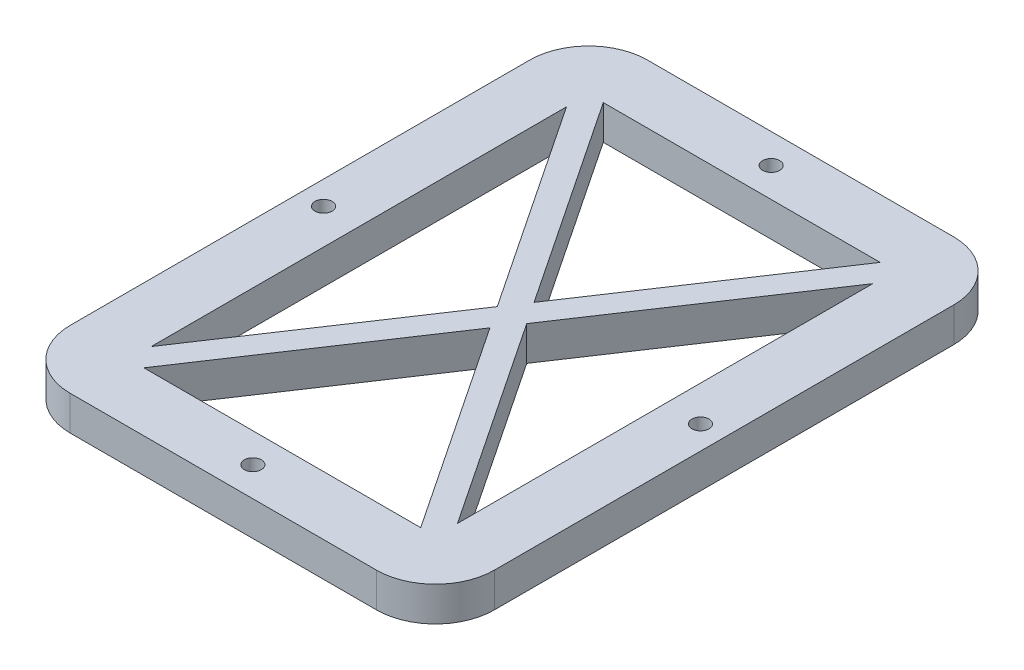
SolidWorks part; units mm, degrees
material "Acrylic (Medium-high impact)"
ref_plane "Front Plane" through (0, 0, 0) normal (0, 0, 1) x (1, 0, 0)
ref_plane "Top Plane" through (0, 0, 0) normal (0, 1, 0) x (1, 0, 0)
ref_plane "Right Plane" through (0, 0, 0) normal (1, 0, 0) x (0, 0, -1)
sketch "Sketch1" plane through (0, 0, 0) normal (0, 1, 0) x (1, 0, 0)
  line L0 (-36, 49) -> (-36, -49) construction
  line L1 (-36, 49) -> (36, 49) construction
  line L2 (-36, -49) -> (36, -49) construction
  line L3 (36, 49) -> (36, -49) construction
  line L4 (-28.5, -39) -> (-23.5, -39)
  line L5 (-28.5, -39) -> (23.5, 39)
  line L6 (-55, 0) -> (55, 0) construction
  line L7 (-74.55, 39) -> (60.5097, 39) construction
  line L8 (-26, 39) -> (26, 39)
  line L9 (-26, 39) -> (-26, -39)
  line L10 (-26, -39) -> (26, -39)
  line L11 (26, 39) -> (26, -39)
  line L12 (-26, 39) -> (26, -39) construction
  line L13 (-26, -39) -> (26, 39) construction
  line L14 (-71.5261, -39) -> (60.5097, -39) construction
  line L15 (-36, 39) -> (-36, -39)
  line L16 (-26, -996.6512) -> (-26, 49003.3488) construction
  line L17 (26, -1000) -> (26, 49000) construction
  line L18 (-26, 49) -> (26, 49)
  line L19 (36, 39) -> (36, -39)
  line L20 (-26, -49) -> (26, -49)
  line L21 (-62.4665, 0) -> (49937.5335, 0) construction
  line L22 (0, 0) -> (0, 50000) construction
  line L23 (-23.5, -39) -> (28.5, 39)
  line L24 (23.5, 39) -> (28.5, 39)
  line L25 (28.5, -39) -> (23.5, -39)
  line L26 (28.5, -39) -> (-23.5, 39)
  line L27 (23.5, -39) -> (-28.5, 39)
  line L28 (-23.5, 39) -> (-28.5, 39)
  arc A0 (-36, 39) -> (-26, 49) centre (-26, 39) cw
  arc A1 (26, 49) -> (36, 39) centre (26, 39) cw
  arc A2 (36, -39) -> (26, -49) centre (26, -39) cw
  arc A3 (-26, -49) -> (-36, -39) centre (-26, -39) cw
  circle A4 centre (0, 44) radius 1.45
  circle A5 centre (0, -44) radius 1.45
  circle A6 centre (-32, 0) radius 1.45
  circle A7 centre (32, 0) radius 1.45
  point P1 (0, 0)
  point P3 (0, 0)
  point P24 (26, 0)
  point P25 (36, 39)
  point P26 (36, -39)
  point P27 (-26, 49)
  point P28 (26, 49)
  point P34 (26, -49)
  point P35 (-26, -49)
  dimension "D6" = 5
  dimension "D7" = 2.9
  dimension "D8" = 2.5
  dimension "D10" = 32
  dimension "D11" = 2.9
  dimension "D1" = 98
  dimension "D2" = 72
  dimension "D3" = 78
  dimension "D4" = 52
extrude "Boss-Extrude1" add sketch "Sketch1" along normal blind 5.85 contours A3 L20 A2 L19 A1 L18 A0 L15 A7 A6 A5 A4 L28 L8 L24 L23 L11 L26 L25 L10 L4 L5 L9 L27 | L23 L27 L5 L9 L4 | L27 L5 L26 L8 L9 | L9 L28 L27 | L9 L5 L4 | L25 L26 L11 | L27 L10 L11 L26 L23 | L27 L23 L26 L5 | L26 L23 L11 L8 L5 | L24 L11 L23 region at (-26.8333, 0, 37.75) region at (-13.3152, 0, 19.9728) region at (-13.3152, 0, -19.9728) region at (0, 0, 0) region at (-26.8333, 0, -37.75) region at (13.3152, 0, 19.9728) region at (13.3152, 0, -19.9728) region at (26.8333, 0, 37.75) region at (26.8333, 0, -37.75) region at (-32.2112, 0, -45.2112)
